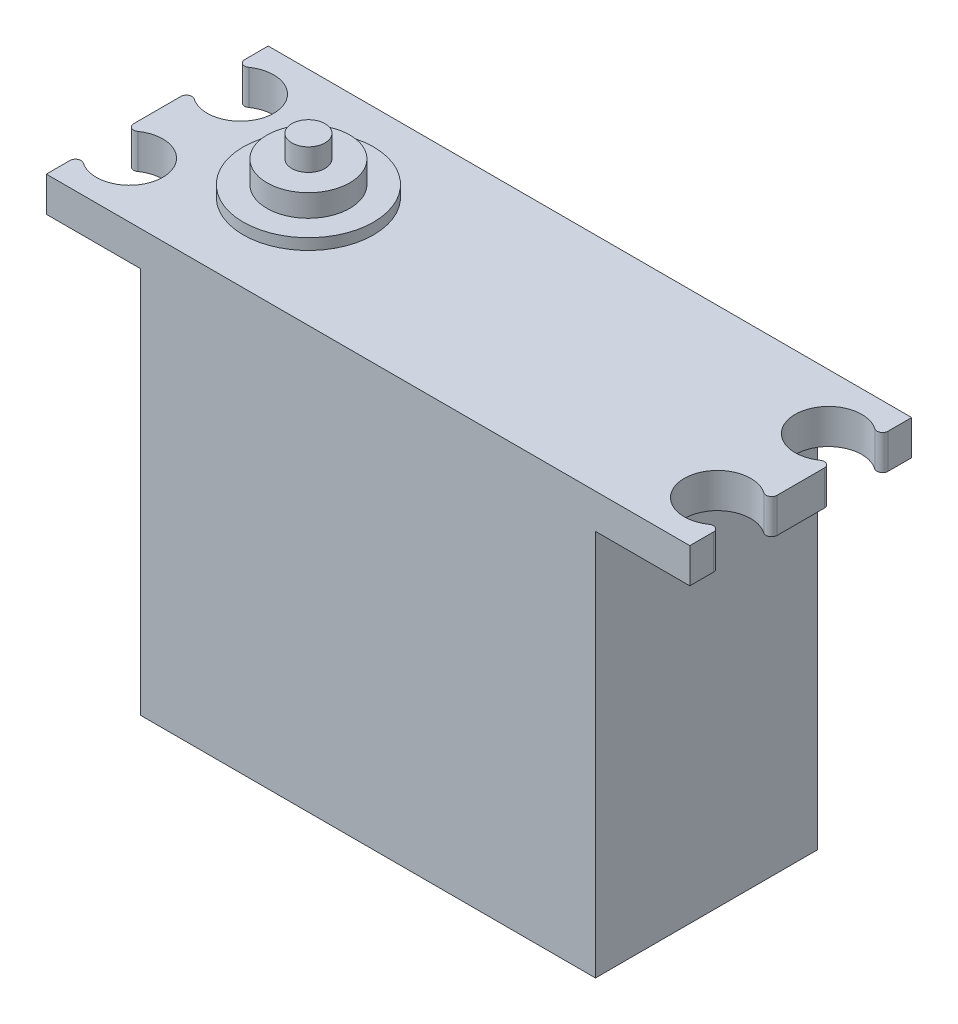
SolidWorks part; units mm, degrees
ref_plane "Front Plane" through (0, 0, 0) normal (0, 0, 1) x (1, 0, 0)
ref_plane "Top Plane" through (0, 0, 0) normal (0, 1, 0) x (1, 0, 0)
ref_plane "Right Plane" through (0, 0, 0) normal (1, 0, 0) x (0, 0, -1)
sketch "Sketch1" plane through (0, 0, 0) normal (0, 0, 1) x (1, 0, 0)
  line L0 (-29, 19) -> (29, 19)
  line L1 (20.5, -19) -> (-20.5, -19)
  line L2 (20.5, -19) -> (20.5, 15.8627)
  line L3 (20.5, 17) -> (-20.5, 17)
  line L4 (-20.5, -19) -> (-20.5, 15.8627)
  line L7 (-20.5, 15.8627) -> (-29, 15.8627)
  line L8 (29, 19) -> (29, 15.8627)
  line L9 (29, 15.8627) -> (20.5, 15.8627)
  line L10 (-29, 19) -> (-29, 15.8627)
  point P0 (0, 0)
  point P6 (0, 17)
  dimension "D1" = 41
  dimension "D2" = 36
extrude "Boss-Extrude1" add sketch "Sketch1" against normal blind 20 contours L0 L8 L9 L2 L1 L4 L7 L10
sketch "Sketch2" plane through (0, 19, 0) normal (0, 1, 0) x (1, 0, 0)
  line L0 (-29, 10) -> (31.146, 10) construction
  line L1 (-29, 20) -> (-29, 0) construction
  line L2 (0, 0) -> (0, 20) construction
  line L3 (-29, 0) -> (29, 0) construction
  line L4 (-29, 20) -> (29, 20) construction
  line L5 (29, 20) -> (29, 0) construction
  circle A0 centre (26.5, 5) radius 3
  circle A1 centre (26.5, 15) radius 3
  circle A2 centre (-26.5, 5) radius 3
  circle A3 centre (-26.5, 15) radius 3
  dimension "D1" = 6
  dimension "D2" = 2.5
  dimension "D3" = 10
extrude "Cut-Extrude2" cut sketch "Sketch2" against normal through all
fillet "Fillet1" radius 0.5 8 edges at (-29, 17.4314, -16.6583) (-29, 17.4314, -13.3417) (-29, 17.4314, -6.6583) (-29, 17.4314, -3.3417) (29, 17.4314, -13.3417) (29, 17.4314, -16.6583) (29, 17.4314, -6.6583) (29, 17.4314, -3.3417)
sketch "Sketch4" plane through (0, 19, 0) normal (0, 1, 0) x (1, 0, 0)
  line L0 (-29, 10) -> (29, 10) construction
  line L1 (-29, 12.1277) -> (-29, 7.8723) construction
  line L2 (29, 12.1277) -> (29, 7.8723) construction
  circle A0 centre (-15.3758, 10) radius 5.8721
extrude "Boss-Extrude2" add sketch "Sketch4" along normal blind 1
sketch "Sketch5" plane through (0, 20, 0) normal (0, 1, 0) x (1, 0, 0)
  circle A0 centre (-15.3758, 10) radius 3.7328
extrude "Boss-Extrude3" add sketch "Sketch5" along normal blind 2
sketch "Sketch8" plane through (0, 22, 0) normal (0, 1, 0) x (1, 0, 0)
  circle A0 centre (-15.3758, 10) radius 1.5
  dimension "D1" = 3
extrude "Boss-Extrude4" add sketch "Sketch8" along normal blind 2
